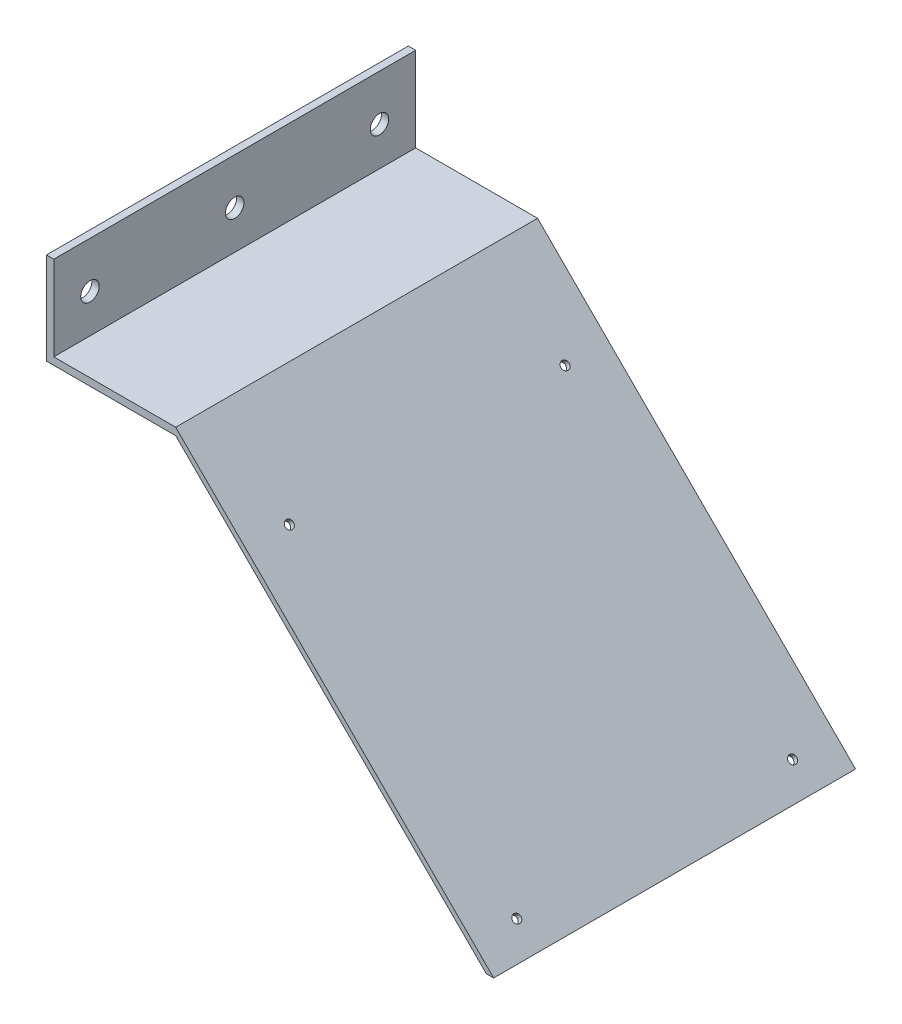
SolidWorks part; units mm, degrees
ref_plane "Front Plane" through (0, 0, 0) normal (0, 0, 1) x (1, 0, 0)
ref_plane "Top Plane" through (0, 0, 0) normal (0, 1, 0) x (1, 0, 0)
ref_plane "Right Plane" through (0, 0, 0) normal (1, 0, 0) x (0, 0, -1)
sketch "Sketch1" plane through (0, 0, 0) normal (0, 0, 1) x (1, 0, 0)
  line L11 (0, 0) -> (85.8336, -85.8336)
  line L12 (0, 2.032) -> (0, 0) construction
  line L13 (0, 0) -> (-35.7216, 0)
  line L14 (0, 0) -> (0, 2.032)
  line L15 (0, 2.032) -> (-35.7216, 2.032)
  line L16 (-35.7216, 0) -> (-35.7216, 2.032)
  line L17 (-35.7216, 0) -> (-33.6896, 0)
  line L18 (-35.7216, 0) -> (-35.7216, 25.4)
  line L19 (-35.7216, 25.4) -> (-33.6896, 25.4)
  line L20 (-33.6896, 0) -> (-33.6896, 25.4)
  line L21 (85.8336, -85.8336) -> (87.8656, -85.8336)
  line L22 (87.8656, -85.8336) -> (0, 2.032)
  line L23 (0, 0) -> (0, -2.9682) construction
  dimension "D1" = 45
  dimension "D2" = 2.032
  dimension "D3" = 35.7216
  dimension "D4" = 121.387
  dimension "D5" = 25.4
extrude "Boss-Extrude1" add sketch "Sketch1" along normal blind 100 contours L12 | L20 L13 L14 L15 | L15 L20 L19 L18 | L13 L20 L15 L16 | L21 L22 L14 L11 region at (43.4268, -42.4068, 0) region at (-16.8448, 1.016, 0) region at (-34.7056, 1.016, 0) region at (-34.7056, 13.716, 0)
sketch "Sketch2" plane through (1.016, 1.016, 0) normal (0.7071, 0.7071, 0) x (0, 0, -1)
  line L0 (-50, -28.087) -> (-50, -113.087) construction
  line L1 (-80, -28.087) -> (-20, -28.087) construction
  line L2 (-80, -28.087) -> (-80, -113.087) construction
  line L3 (-80, -113.087) -> (-20, -113.087) construction
  line L4 (-20, -28.087) -> (-20, -113.087) construction
  line L5 (-75, -35.187) -> (-25, -35.187) construction
  line L6 (-75, -35.187) -> (-75, -105.987) construction
  line L7 (-75, -105.987) -> (-25, -105.987) construction
  line L10 (-25, -35.187) -> (-25, -105.987) construction
  line L11 (-69.455, -33.889) -> (-30.545, -33.889) construction
  line L12 (-69.455, -33.889) -> (-69.455, -107.285) construction
  line L13 (-69.455, -107.285) -> (-30.545, -107.285) construction
  line L14 (-30.545, -33.889) -> (-30.545, -107.285) construction
  line L15 (-80, -70.587) -> (-20, -70.587) construction
  line L16 (-100, -122.8238) -> (-100, 1.4368) construction
  line L18 (-100, -122.8238) -> (0, -122.8238) construction
  line L21 (-88.1, -26.137) -> (-88.1, -115.037) construction
  line L22 (-88.1, -115.037) -> (-11.9, -115.037) construction
  line L23 (-11.9, -115.037) -> (-11.9, -26.137) construction
  line L24 (-11.9, -26.137) -> (-88.1, -26.137) construction
  circle A0 centre (-88.1, -26.137) radius 1.13
  circle A1 centre (-11.9, -26.137) radius 1.13
  circle A2 centre (-11.9, -115.037) radius 1.13
  circle A3 centre (-88.1, -115.037) radius 1.13
  point P6 (-25, -70.587)
  point P10 (-50, -28.087)
  point P11 (0, 0)
  point P13 (-50, -70.587)
  point P17 (-50, -35.187)
  point P23 (-50, -33.889)
  point P24 (-30.545, -70.587)
  point P35 (0, 0)
  point P36 (0, 0)
  point P37 (-50, -26.137)
  point P39 (-11.9, -70.587)
  dimension "D12" = 2.26
  dimension "D11" = 76.2
  dimension "D13" = 88.9
  dimension "D2" = 50
  dimension "D3" = 9.7368
ref_axis "Axis1" through (-9.134, -48.8965, 50) along (1, 0, 0)
extrude "Cut-Extrude1" cut sketch "Sketch2" against normal through all both and the other way through all
hole_wizard "#4-40 Tapped Hole1" positions "3DSketch1" profile "Sketch3" tap size "#4-40" standard "ANSI Inch" end condition through all
sketch3d "3DSketch1"
  point P0 (19.4977, -17.4657, 88.1)
  point P3 (19.4977, -17.4657, 11.9)
  point P6 (82.3594, -80.3274, 11.9)
  point P9 (82.3594, -80.3274, 88.1)
sketch "Sketch3" plane through (19.4977, -17.4657, 88.1) normal (0, 0, 1) x (-0.7071, 0.7071, 0)
  line L0 (0, 0) -> (0, 87.3893)
  line L1 (0, 87.3893) -> (1.1303, 87.3893)
  line L2 (1.1303, 87.3893) -> (1.1303, 0)
  line L5 (1.1303, 0) -> (0, 0)
  line L11 (0, -6.35) -> (0, 107.95) construction
  dimension "Thru Tap Drill Dia." = 2.2606
  dimension "Thru Tap Drill Depth" = 87.3893
cosmetic thread "Hole Thread1" parameters "D2"=2.8448
cosmetic thread "Hole Thread2" parameters "D2"=2.8448
cosmetic thread "Hole Thread3" parameters "D2"=2.8448
cosmetic thread "Hole Thread4" parameters "D2"=2.8448
hole_wizard "1/4-20 Tapped Hole1" positions "Sketch4" profile "Sketch5" tap size "1/4-20" standard "ANSI Inch" end condition through all
sketch "Sketch4" plane through (-35.7216, 0, 0) normal (-1, 0, 0) x (0, 0, 1)
  line L0 (10, 12.7) -> (50, 12.7) construction
  line L1 (50, 12.7) -> (90, 12.7) construction
  line L5 (0, 0) -> (0, 25.4) construction
  point P0 (10, 12.7)
  point P2 (50, 12.7)
  point P4 (90, 12.7)
  dimension "D1" = 80
  dimension "D2" = 10
  dimension "D3" = 12.7
sketch "Sketch5" plane through (-35.7216, 12.7, 10) normal (0, 1, 0) x (0, 0, 1)
  line L0 (0, 0) -> (0, 123.5871)
  line L1 (0, 123.5871) -> (2.5527, 123.5871)
  line L2 (2.5527, 123.5871) -> (2.5527, 0)
  line L5 (2.5527, 0) -> (0, 0)
  line L11 (0, -6.35) -> (0, 107.95) construction
  dimension "Thru Tap Drill Dia." = 5.1054
  dimension "Thru Tap Drill Depth" = 123.5871
cosmetic thread "Hole Thread5" parameters "D2"=6.35
cosmetic thread "Hole Thread6" parameters "D2"=6.35
cosmetic thread "Hole Thread7" parameters "D2"=6.35
equation "\"width\"=100"
equation "\"D1@Boss-Extrude1\"=\"width\""
equation "\"height\"=121.387"
equation "\"D13@Sketch2\"=3.5*25.4"
equation "\"D11@Sketch2\"=3.0*25.4"
